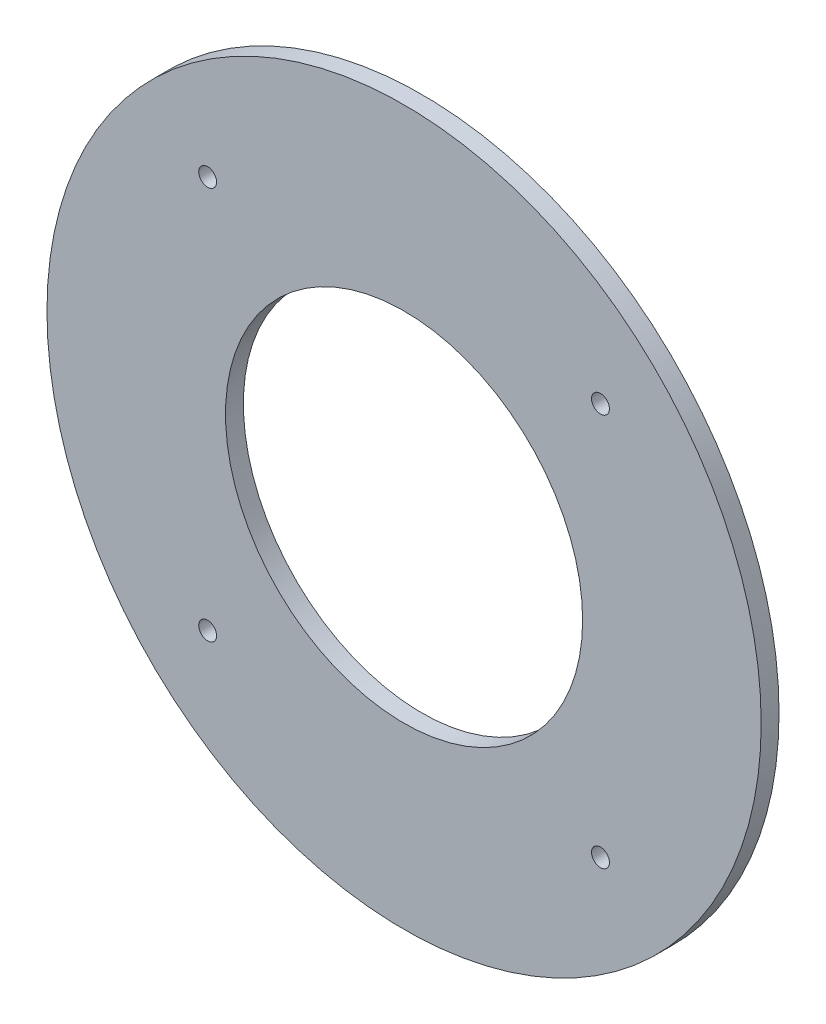
SolidWorks part; units mm, degrees
material "Pine"
ref_plane "Front Plane" through (0, 0, 0) normal (0, 0, 1) x (1, 0, 0)
ref_plane "Top Plane" through (0, 0, 0) normal (0, 1, 0) x (1, 0, 0)
ref_plane "Right Plane" through (0, 0, 0) normal (1, 0, 0) x (0, 0, -1)
sketch "Sketch1" plane through (0, 0, 0) normal (0, 0, 1) x (1, 0, 0)
  circle A0 centre (0, 0) radius 63.5
  circle A1 centre (0, 0) radius 127
  circle A2 centre (-69.85, 69.85) radius 3.175 construction
  circle A3 centre (-69.85, 69.85) radius 3.175
  circle A4 centre (69.85, 69.85) radius 3.175 construction
  circle A5 centre (69.85, 69.85) radius 3.175
  circle A6 centre (-69.85, -69.85) radius 3.175 construction
  circle A7 centre (69.85, -69.85) radius 3.175 construction
  circle A8 centre (-69.85, -69.85) radius 3.175
  circle A9 centre (69.85, -69.85) radius 3.175
  dimension "D1" = 127
  dimension "D2" = 254
extrude "Boss-Extrude1" add sketch "Sketch1" along normal blind 6.35
